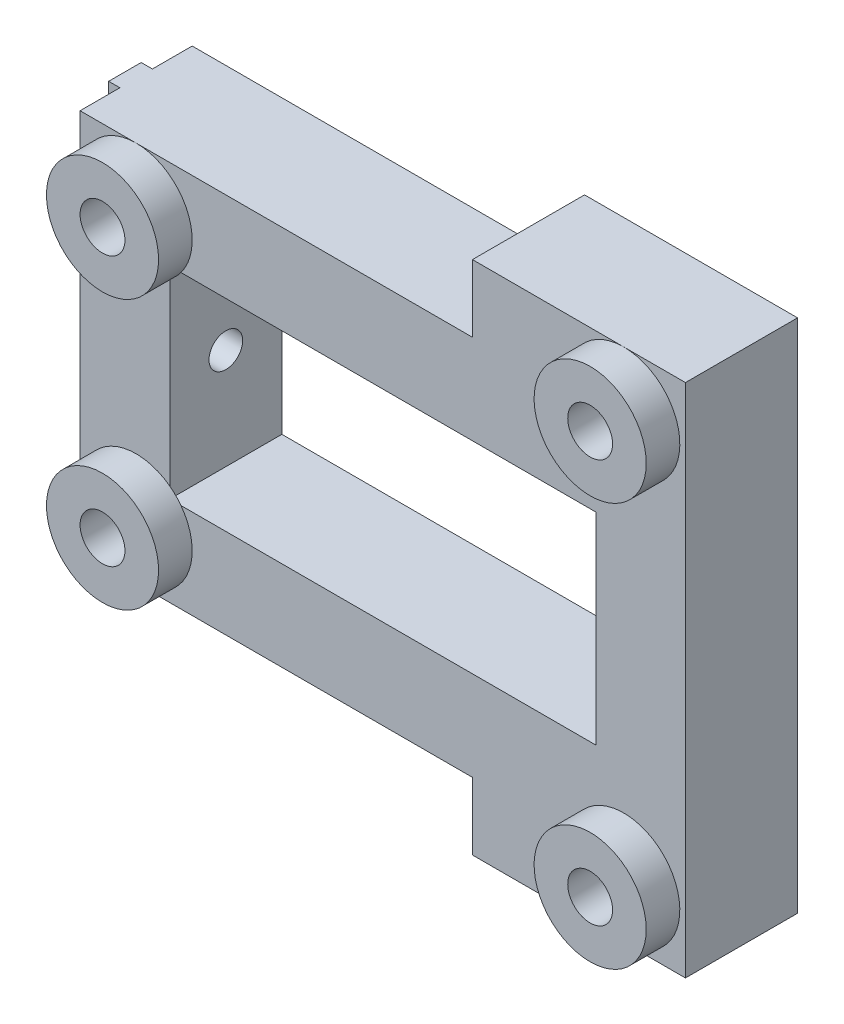
SolidWorks part; units mm, degrees
ref_plane "Plan de face" through (0, 0, 0) normal (0, 0, 1) x (1, 0, 0)
ref_plane "Plan de dessus" through (0, 0, 0) normal (0, 1, 0) x (1, 0, 0)
ref_plane "Plan de droite" through (0, 0, 0) normal (1, 0, 0) x (0, 0, -1)
sketch "Esquisse1" plane through (0, 0, 0) normal (0, 0, 1) x (1, 0, 0)
  line L1 (-27, -23) -> (27, -23)
  line L2 (-27, -23) -> (-27, 23)
  line L3 (-27, 23) -> (27, 23)
  line L4 (27, -23) -> (27, 23)
  point P7 (0, -23)
  point P8 (-27, 0)
  dimension "D1" = 46
  dimension "D2" = 54
extrude "Boss.-Extru.1" add sketch "Esquisse1" along normal blind 10
sketch "Esquisse2" plane through (0, 0, 10) normal (0, 0, 1) x (1, 0, 0)
  line L1 (-27, -23) -> (27, -23) construction
  line L2 (27, 23) -> (-27, 23) construction
  line L3 (-27, 23) -> (-27, -23) construction
  circle A0 centre (-22, -12) radius 2
  circle A1 centre (-22, 12) radius 2
  circle A2 centre (21.5, 18) radius 2
  circle A3 centre (21.5, -18) radius 2
  dimension "D1" = 4
  dimension "D2" = 48.5
  dimension "D3" = 5
  dimension "D4" = 11
  dimension "D5" = 11
  dimension "D6" = 5
  dimension "D7" = 5
  dimension "D8" = 24
  dimension "D9" = 36
extrude "Enlèv. mat.-Extru.1" cut sketch "Esquisse2" against normal through all
sketch "Esquisse3" plane through (0, 0, 10) normal (0, 0, 1) x (1, 0, 0)
  circle A0 centre (-22, 12) radius 5
  circle A1 centre (-22, -12) radius 5
  circle A2 centre (21.5, -18) radius 5
  circle A3 centre (21.5, 18) radius 5
  circle A4 centre (21.5, 18) radius 2 construction
  circle A5 centre (-22, 12) radius 2 construction
  circle A6 centre (-22, -12) radius 2 construction
  circle A7 centre (21.5, -18) radius 2 construction
  dimension "D1" = 10
extrude "Boss.-Extru.2" add sketch "Esquisse3" along normal blind 3
sketch "Esquisse4" plane through (0, -23, 0) normal (0, -1, 0) x (1, 0, 0)
  line L0 (-27, 10) -> (21.5, 10) construction
  line L1 (8, 10) -> (-27, 10)
  line L2 (8, 10) -> (8, 0)
  line L3 (8, 0) -> (-27, 0)
  line L4 (-27, 10) -> (-27, 0)
  dimension "D2" = 35
extrude "Enlèv. mat.-Extru.2" cut sketch "Esquisse4" against normal blind 6
sketch "Esquisse6" plane through (0, 23, 0) normal (0, 1, 0) x (1, 0, 0)
  line L0 (21.5, -10) -> (-27, -10) construction
  line L1 (-27, 0) -> (8, 0)
  line L2 (-27, 0) -> (-27, -10)
  line L3 (-27, -10) -> (8, -10)
  line L4 (8, 0) -> (8, -10)
  line L5 (-27, -10) -> (-27, 0) construction
  line L6 (27, 0) -> (-27, 0) construction
  line L7 (16.5, -10) -> (26.5, -10) construction
extrude "Enlèv. mat.-Extru.3" cut sketch "Esquisse6" against normal blind 6
sketch "Esquisse7" plane through (-27, 0, 0) normal (-1, 0, 0) x (0, 0, 1)
  line L1 (3.55, 17) -> (6.45, 17)
  line L2 (3.55, 17) -> (3.55, -17)
  line L3 (3.55, -17) -> (6.45, -17)
  line L4 (6.45, 17) -> (6.45, -17)
  line L9 (0, 17) -> (10, 17) construction
  line L10 (10, -17) -> (0, -17) construction
  point P4 (5, 17)
  point P10 (5, 17)
  dimension "D1" = 2.9
extrude "Boss.-Extru.3" add sketch "Esquisse7" along normal blind 1
sketch "Esquisse10" plane through (0, 0, 10) normal (0, 0, 1) x (1, 0, 0)
  line L0 (-22, 17) -> (8, 17) construction
  line L1 (-19, 9) -> (19, 9)
  line L2 (-19, 9) -> (-19, -9)
  line L3 (-19, -9) -> (19, -9)
  line L4 (19, 9) -> (19, -9)
  line L5 (8, -17) -> (-22, -17) construction
  line L6 (-27, -17) -> (-27, 17) construction
  line L7 (27, -23) -> (27, 23) construction
  dimension "D1" = 8
  dimension "D2" = 8
  dimension "D3" = 8
  dimension "D4" = 8
extrude "Enlèv. mat.-Extru.5" cut sketch "Esquisse10" against normal through all
sketch "Esquisse8" plane through (-28, 0, 0) normal (-1, 0, 0) x (0, 0, 1)
  line L0 (6.45, 17) -> (3.55, 17) construction
  line L1 (3.55, -17) -> (6.45, -17) construction
  line L2 (6.45, -17) -> (6.45, 17) construction
  circle A0 centre (5, 0) radius 1.5
  point P7 (5, 17)
  point P12 (6.45, 0)
  dimension "D1" = 3
extrude "Enlèv. mat.-Extru.4" cut sketch "Esquisse8" against normal up to next
sketch "Esquisse11" plane through (0, 0, 10) normal (0, 0, -1) x (-1, 0, 0)
  circle A0 centre (-21.5, 18) radius 2
  circle A1 centre (22, 12) radius 2
  circle A2 centre (22, -12) radius 2
  circle A3 centre (-21.5, -18) radius 2
  circle A4 centre (-21.5, -18) radius 2 construction
  circle A5 centre (-21.5, 18) radius 2 construction
  circle A6 centre (22, -12) radius 2 construction
  circle A7 centre (22, 12) radius 2 construction
extrude "Enlèv. mat.-Extru.6" cut sketch "Esquisse11" against normal through all
